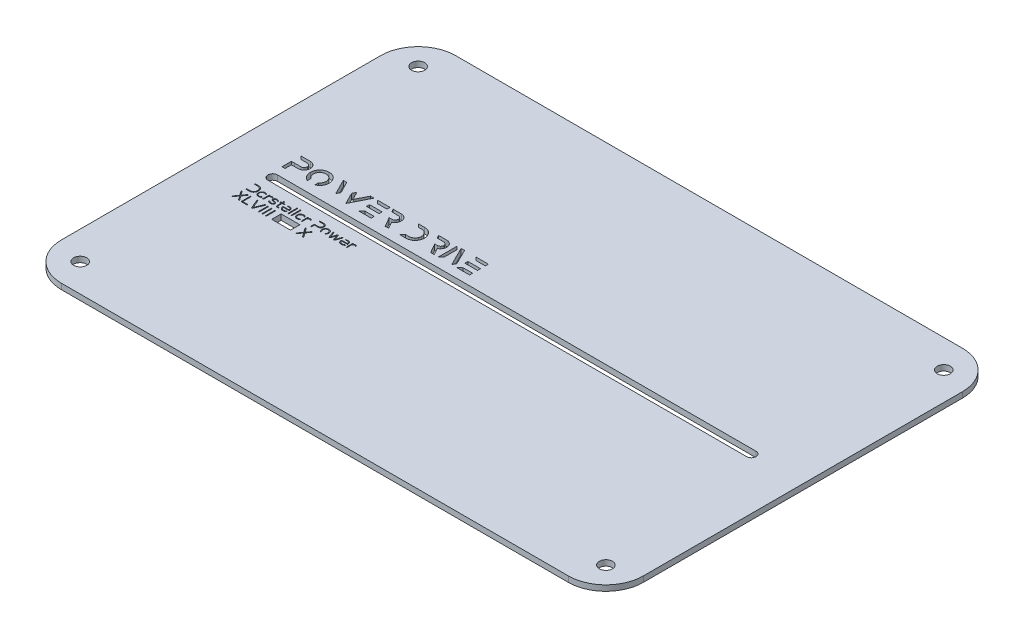
SolidWorks part; units mm, degrees
ref_plane "Front Plane" through (0, 0, 0) normal (0, 0, 1) x (1, 0, 0)
ref_plane "Top Plane" through (0, 0, 0) normal (0, 1, 0) x (1, 0, 0)
ref_plane "Right Plane" through (0, 0, 0) normal (1, 0, 0) x (0, 0, -1)
sketch "Sketch1" plane through (0, 0, 0) normal (0, 1, 0) x (1, 0, 0)
  line L1 (155, 105) -> (-155, 105)
  line L2 (155, 105) -> (155, -105)
  line L3 (155, -105) -> (-155, -105)
  line L4 (-155, 105) -> (-155, -105)
  line L5 (155, 105) -> (-155, -105) construction
  line L6 (155, -105) -> (-155, 105) construction
  circle A0 centre (-140, 90) radius 3.5
  circle A1 centre (140, 90) radius 3.5
  circle A2 centre (140, -90) radius 3.5
  circle A3 centre (-140, -90) radius 3.5
  point P0 (0, 0)
  dimension "D3" = 15
  dimension "D4" = 7
  dimension "D5" = 15
  dimension "D6" = 15
  dimension "D7" = 15
  dimension "D8" = 15
  dimension "D9" = 15
  dimension "D10" = 15
  dimension "D11" = 15
  dimension "D1" = 310
  dimension "D2" = 210
extrude "Boss-Extrude1" add sketch "Sketch1" along normal blind 3
fillet "Fillet1" radius 20 4 edges at (155, 1.5, 105) (155, 1.5, -105) (-155, 1.5, -105) (-155, 1.5, 105)
sketch "Sketch2" plane through (0, 3, 0) normal (0, 1, 0) x (1, 0, 0)
  line L0 (-130, 2.5) -> (-130, 7.5) construction
  line L1 (130, 2.5) -> (-130, 2.5)
  line L2 (130, 2.5) -> (130, -2.5)
  line L3 (130, -2.5) -> (-130, -2.5)
  line L4 (-130, 2.5) -> (-130, -2.5)
  line L5 (130, 2.5) -> (-130, -2.5) construction
  line L6 (130, -2.5) -> (-130, 2.5) construction
  line L7 (-130, 7.5) -> (92.6975, 7.5) construction
  line L8 (-130, -2.5) -> (-130, -12.5) construction
  line L9 (-130, -12.5) -> (92.6975, -12.5) construction
  line L10 (-130, -12.5) -> (-130, -19.5) construction
  line L11 (-130, -19.5) -> (92.6975, -19.5) construction
  line L13 (-108.4862, -19.5) -> (-98.4862, -19.5)
  line L14 (-108.4862, -19.5) -> (-108.4862, -14.5)
  line L15 (-108.4862, -14.5) -> (-98.4862, -14.5)
  line L16 (-98.4862, -19.5) -> (-98.4862, -14.5)
  text T0 "POWER DRIVE" font "Anurati" height 10
  text T1 "Dcrstellcr Power" font "Nexa Book" height 5
  text T2 "XLVIII        X" font "Nexa Book" height 5
  point P1 (0, 0)
  dimension "D1" = 5
  dimension "D2" = 260
  dimension "D3" = 5
  dimension "D4" = 10
  dimension "D5" = 7
  dimension "D6" = 5
  dimension "D7" = 10
extrude "Cut-Extrude1" cut sketch "Sketch2" against normal through all
fillet "Fillet2" radius 2.5 4 edges at (130, 1.5, 2.5) (130, 1.5, -2.5) (-130, 1.5, 2.5) (-130, 1.5, -2.5)
sketch "Sketch3" plane through (0, 3, 0) normal (0, 1, 0) x (1, 0, 0)
  line L0 (-127.5391, -12.0428) -> (-128.818, -12.0428) construction
  line L1 (-127.7928, -12.0428) -> (-131.6937, -12.0428)
  line L2 (-127.7928, -12.0428) -> (-127.7928, -7.9489)
  line L3 (-127.7928, -7.9489) -> (-131.6937, -7.9489)
  line L4 (-131.6937, -12.0428) -> (-131.6937, -7.9489)
  line L5 (-128.818, -7.9489) -> (-127.5387, -7.9489) construction
  line L6 (-108.2506, -10.5272) -> (-110.8619, -10.5272) construction
  line L7 (-109.5459, -10.5272) -> (-111.6478, -10.5272)
  line L8 (-109.5459, -10.5272) -> (-109.5459, -9.3338)
  line L9 (-109.5459, -9.3338) -> (-111.6478, -9.3338)
  line L10 (-111.6478, -10.5272) -> (-111.6478, -9.3338)
  line L11 (-77.1468, -10.5272) -> (-79.7581, -10.5272) construction
  line L12 (-87.6501, -12.9604) -> (-89.6501, -12.9604)
  line L13 (-87.6501, -12.9604) -> (-87.6501, -11.2632)
  line L14 (-87.6501, -11.2632) -> (-89.6501, -11.2632)
  line L15 (-89.6501, -12.9604) -> (-89.6501, -11.2632)
  line L16 (-87.6501, -12.9604) -> (-89.6501, -11.2632) construction
  line L17 (-87.6501, -11.2632) -> (-89.6501, -12.9604) construction
  line L18 (-78.4422, -10.5272) -> (-80.4936, -10.5272)
  line L19 (-78.4422, -10.5272) -> (-78.4422, -9.3338)
  line L20 (-78.4422, -9.3338) -> (-80.4936, -9.3338)
  line L21 (-80.4936, -10.5272) -> (-80.4936, -9.3338)
  line L27 (-112.8635, 11.6067) -> (-116.8635, 6.6393) construction
  line L28 (-112.8635, 6.6393) -> (-116.8635, 11.6067) construction
  spline S3 degree 3 poles (-110.8619, -10.5272) (-110.8551, -10.4804) (-110.8417, -10.3888) (-110.8097, -10.2568) (-110.768, -10.1334) (-110.7191, -10.0181) (-110.6611, -9.911) (-110.5942, -9.813) (-110.518, -9.7238) (-110.435, -9.6423) (-110.344, -9.5704) (-110.2471, -9.5069) (-110.1433, -9.4549) (-110.0353, -9.41) (-109.9211, -9.3758) (-109.8009, -9.353) (-109.6754, -9.3365) (-109.5896, -9.3347) (-109.5459, -9.3338) knots 0 0 0 0 0.072195 0.141201 0.206982 0.270828 0.332257 0.39257 0.451677 0.510961 0.569879 0.628594 0.687411 0.746862 0.807036 0.868999 0.933405 1 1 1 1 construction
  spline S4 degree 3 poles (-79.7581, -10.5272) (-79.7513, -10.4804) (-79.7379, -10.3888) (-79.7059, -10.2568) (-79.6642, -10.1334) (-79.6153, -10.0181) (-79.5573, -9.911) (-79.4904, -9.813) (-79.4143, -9.7238) (-79.3312, -9.6423) (-79.2402, -9.5704) (-79.1434, -9.5069) (-79.0395, -9.4549) (-78.9315, -9.41) (-78.8173, -9.3758) (-78.6971, -9.353) (-78.5716, -9.3365) (-78.4858, -9.3347) (-78.4421, -9.3338) knots 0 0 0 0 0.072195 0.141201 0.206982 0.270828 0.332257 0.39257 0.451677 0.510961 0.569879 0.628594 0.687411 0.746862 0.807036 0.868999 0.933405 1 1 1 1 construction
  point P19 (-88.6501, -12.1118)
  point P29 (-114.8635, 9.123)
  dimension "D1" = 2
  dimension "D2" = 4
extrude "Boss-Extrude2" add sketch "Sketch3" against normal blind 3
sketch "Sketch4" plane through (0, 3, 0) normal (0, 1, 0) x (1, 0, 0)
  line L0 (-92.6905, -10.3954) -> (-94.4193, -10.3954) construction
  line L1 (-93.5549, -10.3954) -> (-96.4921, -10.3954)
  line L2 (-93.5549, -10.3954) -> (-93.5549, -7.9489)
  line L3 (-93.5549, -7.9489) -> (-96.4921, -7.9489)
  line L4 (-96.4921, -10.3954) -> (-96.4921, -7.9489)
  line L5 (-94.4193, -7.9489) -> (-92.6898, -7.9489) construction
  line L7 (-112.8635, 5.8901) -> (-116.8635, 5.8901)
  line L8 (-112.8635, 5.8901) -> (-112.8635, 12.3559)
  line L9 (-112.8635, 12.3559) -> (-116.8635, 12.3559)
  line L10 (-116.8635, 5.8901) -> (-116.8635, 12.3559)
  line L11 (-112.8635, 5.8901) -> (-116.8635, 12.3559) construction
  line L12 (-112.8635, 12.3559) -> (-116.8635, 5.8901) construction
  point P8 (-114.8635, 9.123)
  dimension "D1" = 4
extrude "Boss-Extrude3" add sketch "Sketch4" against normal blind 3
